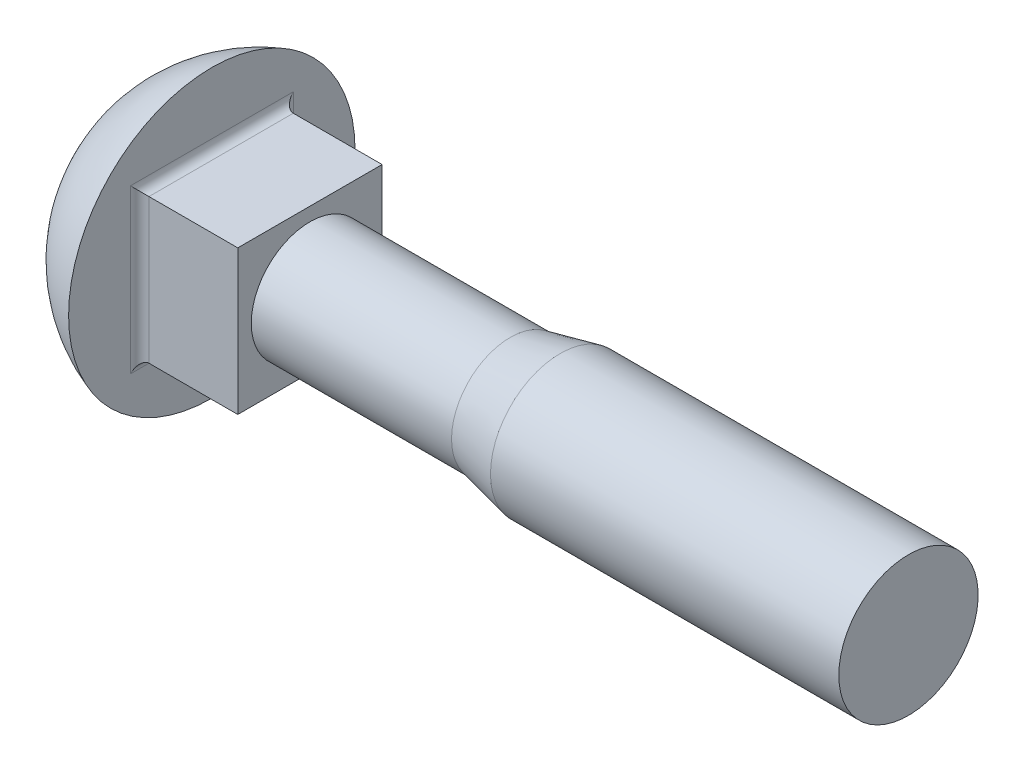
SolidWorks part; units mm, degrees
ref_plane "Front" through (0, 0, 0) normal (0, 0, 1) x (1, 0, 0)
ref_plane "Top" through (0, 0, 0) normal (0, 1, 0) x (1, 0, 0)
ref_plane "Right" through (0, 0, 0) normal (1, 0, 0) x (0, 0, -1)
sketch "Sketch1" plane through (0, 0, 0) normal (0, 0, 1) x (1, 0, 0)
  line L0 (-31.4843, 0) -> (38.6484, 0) construction
  line L1 (68.9, 0) -> (68.9, 6)
  line L2 (68.9, 6) -> (8.9, 6)
  line L3 (8.9, 6) -> (8.9, 12.3365)
  line L4 (68.9, 0) -> (0, 0)
  arc A0 (8.9, 12.3365) -> (0, 0) centre (13, 0) ccw
  dimension "l" = 60
revolve "Base" add sketch "Sketch1" angle 360 about L0
cosmetic thread "ThreadCosmetic1" [suppressed] parameters "D2"=10.106
ref_plane "Plane1" through (38.9, 0, 0) normal (1, 0, 0) x (0, 0, -1)
sketch "Sketch2" plane through (8.9, 0, 0) normal (1, 0, 0) x (0, 0, -1)
  line L1 (6.215, -6.215) -> (6.215, 6.215)
  line L2 (6.215, 6.215) -> (-6.215, 6.215)
  line L3 (-6.215, 6.215) -> (-6.215, -6.215)
  line L4 (-6.215, -6.215) -> (6.215, -6.215)
  circle A1 centre (0, 0) radius 6.215 construction
  dimension "Ss" = 12.43
extrude "Neck" add sketch "Sketch2" along normal blind 8.45
sketch "Sketch5" plane through (0, 0, 0) normal (0, 0, 1) x (1, 0, 0)
  line L0 (17.35, 5.053) -> (34.6, 5.053)
  line L1 (17.35, -6) -> (17.35, 6) construction
  line L2 (34.6, 5.053) -> (38.9, 6)
  line L3 (68.9, 6) -> (17.35, 6) construction
  line L4 (38.9, 6) -> (17.35, 6)
  line L5 (17.35, 6) -> (17.35, 5.053)
  line L6 (68.9, -6) -> (68.9, 6) construction
  line L7 (0, 0) -> (82.6115, 0) construction
  dimension "D1" = 30
  dimension "D3" = 10.106
revolve "Cut-Revolve1" cut sketch "Sketch5" angle 360 about L7
fillet "HeadFillet" radius 0.8 4 edges at (8.9, 0, -6.215) (8.9, -6.215, 0) (8.9, 0, 6.215) (8.9, 6.215, 0)
sketch "Sketch4" plane through (0, 0, 0) normal (0, 0, 1) x (1, 0, 0)
  line L0 (68.6292, 6.2) -> (69.1707, 6.2)
  line L1 (69.1707, 6.2) -> (69.1707, 6)
  line L2 (69.1707, 6) -> (68.9, 5.531)
  line L3 (68.6292, 6) -> (68.9, 5.531)
  line L4 (68.6292, 6.2) -> (68.6292, 6)
  line L5 (-64.5053, 0) -> (64.5053, 0) construction
  line L6 (68.6292, 6) -> (69.1707, 6) construction
  line L7 (68.9, 6) -> (68.9, 5.531) construction
  line L8 (68.9, -6) -> (68.9, 6) construction
  point P5 (68.9, 6.2)
  dimension "D3" = 12
  dimension "D1" = 73
revolve "Cut-Revolve10" [suppressed] cut sketch "Sketch4" angle 360 about L5
pattern_linear "LPattern10" [suppressed] count 73 spacing 0.704 along (-1, 0, 0) of bodies 104
equation "\"D3@LPattern10\" = \"D2@Sketch4\" * 1.3"
equation "\"D1@LPattern10\" = (\"l@Sketch1\" - \"k1@Neck\"  )  / \"D3@LPattern10\""
equation "\"D3@Sketch5\" = \"D2@ThreadCosmetic1\""
equation "\"D1@Sketch5\" = \"b@Plane1\""
equation "\"D3@Sketch4\" = \"d@Sketch1\""
